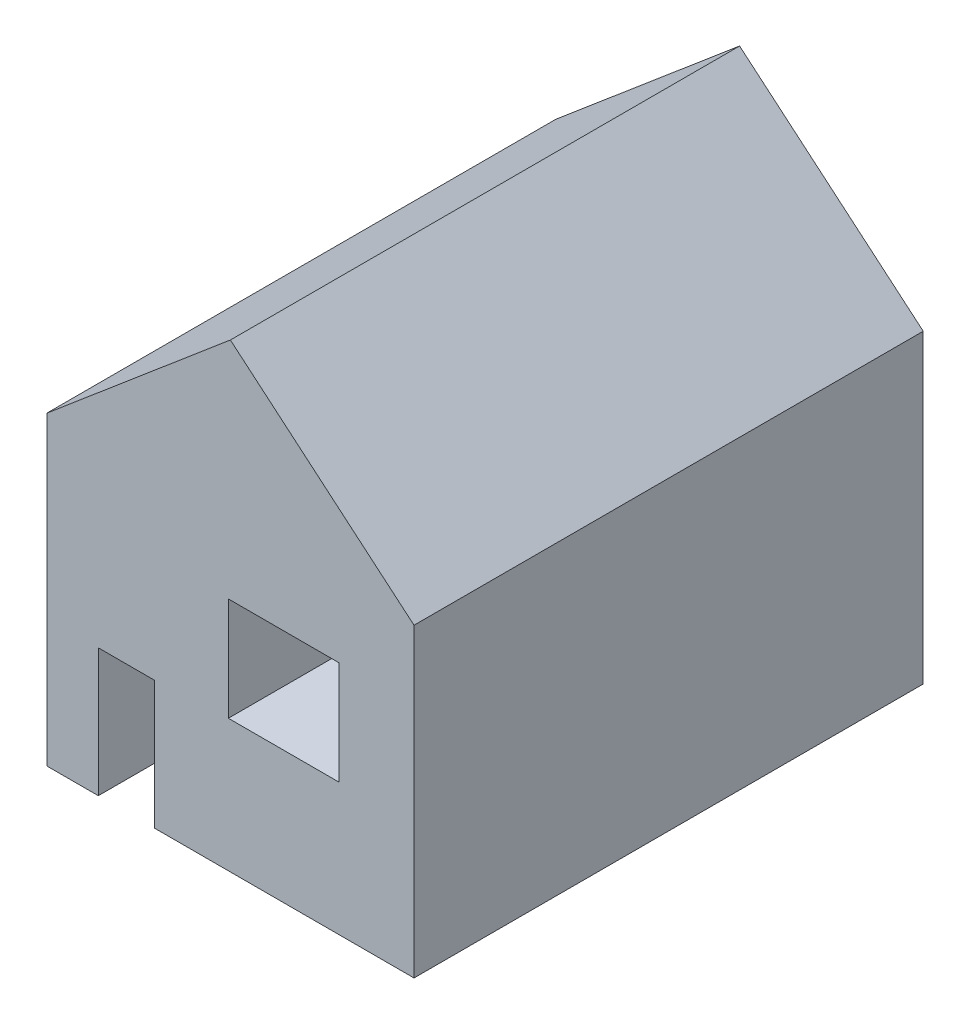
SolidWorks part; units mm, degrees
material "Oak"
ref_plane "Front Plane" through (0, 0, 0) normal (0, 0, 1) x (1, 0, 0)
ref_plane "Top Plane" through (0, 0, 0) normal (0, 1, 0) x (1, 0, 0)
ref_plane "Right Plane" through (0, 0, 0) normal (1, 0, 0) x (0, 0, -1)
sketch "Sketch1" plane through (0, 0, 0) normal (0, 0, 1) x (1, 0, 0)
  line L0 (-82.8898, 24.2439) -> (-54.0409, 48.6232)
  line L9 (-82.8898, 24.2439) -> (-25.192, 24.2439)
  line L10 (-82.8898, 24.2439) -> (-82.8898, -23.7561)
  line L11 (-82.8898, -23.7561) -> (-25.192, -23.7561)
  line L12 (-25.192, 24.2439) -> (-25.192, -23.7561)
  line L13 (-54.0409, 48.6232) -> (-25.192, 24.2439)
  line L14 (-74.7898, -23.7561) -> (-74.7898, -3.6296)
  line L15 (-74.7898, -3.6296) -> (-65.9867, -3.6296)
  line L16 (-65.9867, -3.6296) -> (-65.9867, -23.7561)
  line L17 (-51.3591, 10.2393) -> (-51.3591, 0)
  line L18 (-51.3591, 0) -> (-39.9821, 0)
  line L19 (-39.9821, 0) -> (-39.9821, 10.2393)
  line L20 (-39.9821, 10.2393) -> (-51.3591, 10.2393)
  line L21 (-82.8898, 24.2439) -> (-25.192, 24.2439)
  line L22 (-54.0409, 48.6232) -> (-82.8898, 24.2439)
  line L23 (-36.9821, -3) -> (-36.9821, 13.2393)
  line L24 (-36.9821, 13.2393) -> (-54.3591, 13.2393)
  line L25 (-54.3591, 13.2393) -> (-54.3591, -3)
  line L26 (-54.3591, -3) -> (-36.9821, -3)
  circle A0 centre (-67.5559, -14.8549) radius 0.6847
  dimension "D2" = 48
  dimension "D3" = 8.1
  dimension "D1" = 3
extrude "Boss-Extrude1" add sketch "Sketch1" against normal blind 80 contours L15 L16 L11 L12 L9 L10 L14 L26 L25 L24 L23 region at (-54.0409, 23.4934, 0)
sketch "Sketch2" plane through (0, 0, 0) normal (0, 0, 1) x (1, 0, 0)
extrude "Boss-Extrude2" add sketch "Sketch1<6>" against normal blind 80 contours L13 L0 L9 region at (-54.0409, 32.3703, 0)
sketch "Sketch1<6>" plane through (0, 0, 0) normal (0, 0, 1) x (1, 0, 0) same geometry as "Sketch1"
